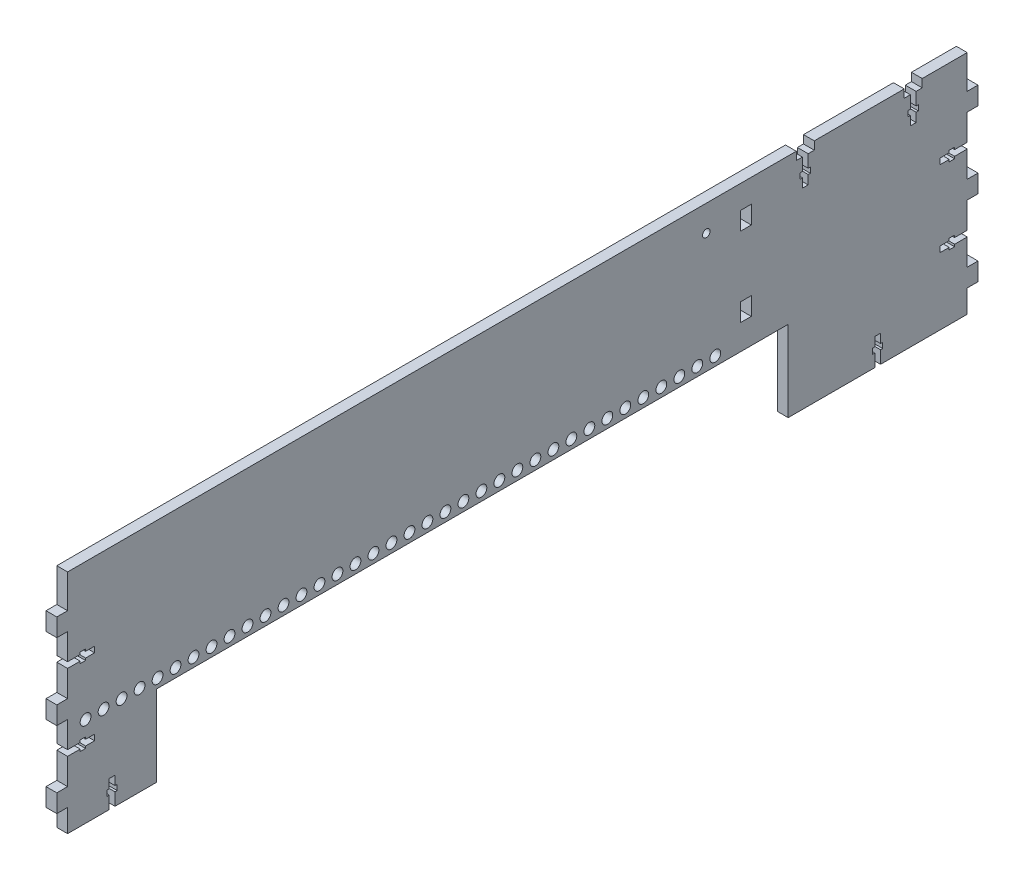
SolidWorks part; units mm, degrees
ref_plane "Front Plane" through (0, 0, 0) normal (0, 0, 1) x (1, 0, 0)
ref_plane "Top Plane" through (0, 0, 0) normal (0, 1, 0) x (1, 0, 0)
ref_plane "Right Plane" through (0, 0, 0) normal (1, 0, 0) x (0, 0, -1)
sketch "Sketch1" plane through (0, 0, 0) normal (1, 0, 0) x (0, 0, -1)
  line L1 (-250, -63) -> (250, -63)
  line L2 (-250, -63) -> (-250, 63)
  line L3 (-250, 63) -> (250, 63)
  line L4 (250, -63) -> (250, 63)
  line L5 (-250, -63) -> (250, 63) construction
  line L6 (-250, 63) -> (250, -63) construction
  point P0 (0, 0)
  dimension "D1" = 126
  dimension "D2" = 500
extrude "Boss-Extrude1" add sketch "Sketch1" along normal blind 6
sketch "Sketch4" plane through (0, 0, 250) normal (0, 0, 1) x (1, 0, 0)
  line L0 (0, 63) -> (0, -63) construction
  line L1 (0, 44.3321) -> (6, 44.3321)
  line L2 (0, 44.3321) -> (0, 34.3321)
  line L3 (0, 34.3321) -> (6, 34.3321)
  line L4 (6, 44.3321) -> (6, 34.3321)
  line L5 (6, 63) -> (6, -63) construction
  line L6 (0, 34.3321) -> (6, 34.3321) construction
  line L7 (0, -69) -> (0, 63) construction
  line L8 (6, 44.3321) -> (0, 44.3321) construction
  line L9 (0, -8) -> (6, -8) construction
  line L10 (0, -8) -> (6, -8)
  line L11 (0, -8) -> (0, 2)
  line L12 (0, 2) -> (6, 2)
  line L13 (6, -8) -> (6, 2)
  line L14 (6, -69) -> (6, 63) construction
  line L15 (6, 2) -> (0, 2) construction
  line L16 (6, -40.3321) -> (0, -40.3321) construction
  line L17 (0, -50.3321) -> (6, -50.3321)
  line L18 (0, -50.3321) -> (0, -40.3321)
  line L19 (0, -40.3321) -> (6, -40.3321)
  line L20 (6, -50.3321) -> (6, -40.3321)
  line L21 (0, -50.3321) -> (6, -50.3321) construction
extrude "Boss-Extrude2" add sketch "Sketch4" along normal blind 6
sketch "Sketch5" plane through (0, 0, 0) normal (-1, 0, 0) x (0, 0, 1)
  line L1 (250, 19.7661) -> (250, 16.5661) construction
  line L3 (250, 19.7661) -> (250, 16.5661) construction
  line L4 (250, -22.5661) -> (250, -25.7661) construction
  line L5 (250, -22.5661) -> (250, -25.7661) construction
  line L6 (250, 18.1661) -> (235, 18.1661) construction
  line L7 (250, -24.1661) -> (235, -24.1661) construction
  line L8 (250, -22.5661) -> (243, -22.5661)
  line L9 (250, 19.7661) -> (243, 19.7661)
  line L10 (250, -25.7661) -> (243, -25.7661)
  line L11 (250, 16.5661) -> (243, 16.5661)
  line L12 (250, -22.5661) -> (250, -25.7661)
  line L13 (235, -22.5661) -> (235, -25.7661)
  line L14 (250, 19.7661) -> (250, 16.5661)
  line L15 (235, 19.7661) -> (235, 16.5661)
  line L16 (240, 16.5661) -> (235, 16.5661)
  line L17 (243, 15.3661) -> (240, 15.3661)
  line L18 (243, 15.3661) -> (243, 16.5661)
  line L19 (243, 20.9661) -> (240, 20.9661)
  line L20 (240, 15.3661) -> (240, 16.5661)
  line L21 (243, 15.3661) -> (240, 20.9661) construction
  line L22 (243, 20.9661) -> (240, 15.3661) construction
  line L23 (243, -26.9661) -> (240, -26.9661)
  line L24 (243, -26.9661) -> (243, -25.7661)
  line L25 (243, -21.3661) -> (240, -21.3661)
  line L26 (240, -26.9661) -> (240, -25.7661)
  line L27 (243, -26.9661) -> (240, -21.3661) construction
  line L28 (243, -21.3661) -> (240, -26.9661) construction
  line L29 (250, 16.5661) -> (235, 16.5661) construction
  line L30 (243, 19.7661) -> (243, 20.9661)
  line L31 (240, 19.7661) -> (235, 19.7661)
  line L32 (250, 19.7661) -> (235, 19.7661) construction
  line L33 (240, 19.7661) -> (240, 20.9661)
  line L34 (240, -22.5661) -> (235, -22.5661)
  line L35 (250, -22.5661) -> (235, -22.5661) construction
  line L36 (240, -22.5661) -> (240, -21.3661)
  line L37 (240, -25.7661) -> (235, -25.7661)
  line L38 (250, -25.7661) -> (235, -25.7661) construction
  line L39 (243, -22.5661) -> (243, -21.3661)
  point P20 (241.5, 18.1661)
  point P25 (241.5, -24.1661)
  line M35 (250, -40.3321) -> (250, -8)
  line M39 (250, 2) -> (250, 34.3321)
  dimension "D3" = 1.6
  dimension "D4" = 7
  dimension "D5" = 3
  dimension "D6" = 5.6
  dimension "D1" = 15
  dimension "D7" = 7
  dimension "D8" = 3
  dimension "D9" = 5.6
  dimension "D2" = 1.6
extrude "Cut-Extrude3" cut sketch "Sketch5" against normal up to next contours L12 | L8 L39 L25 L36 L34 L13 L37 L26 L23 L24 L10 M35 | L33 L31 L15 L16 L20 L17 L18 L11 L9 L30 L19 M39 region at (0, -24.1661, 242.3696) region at (0, 18.1661, 242.3696)
sketch "Sketch6" plane through (0, 0, -250) normal (0, 0, -1) x (-1, 0, 0)
  line L0 (0, 44.3321) -> (0, 34.3321) construction
  line L1 (0, 34.3321) -> (-6, 34.3321) construction
  line L2 (-6, 34.3321) -> (-6, 44.3321) construction
  line L3 (-6, 44.3321) -> (0, 44.3321) construction
  line L4 (0, 2) -> (0, -8) construction
  line L5 (0, -8) -> (-6, -8) construction
  line L6 (-6, -8) -> (-6, 2) construction
  line L7 (-6, 2) -> (0, 2) construction
  line L8 (0, -40.3321) -> (0, -50.3321) construction
  line L9 (0, -50.3321) -> (-6, -50.3321) construction
  line L10 (-6, -50.3321) -> (-6, -40.3321) construction
  line L11 (-6, -40.3321) -> (0, -40.3321) construction
  line L12 (0, 44.3321) -> (0, 34.3321)
  line L13 (0, 34.3321) -> (-6, 34.3321)
  line L14 (-6, 34.3321) -> (-6, 44.3321)
  line L15 (-6, 44.3321) -> (0, 44.3321)
  line L16 (0, 2) -> (0, -8)
  line L17 (0, -8) -> (-6, -8)
  line L18 (-6, -8) -> (-6, 2)
  line L19 (-6, 2) -> (0, 2)
  line L20 (0, -40.3321) -> (0, -50.3321)
  line L21 (0, -50.3321) -> (-6, -50.3321)
  line L22 (-6, -50.3321) -> (-6, -40.3321)
  line L23 (-6, -40.3321) -> (0, -40.3321)
extrude "Boss-Extrude3" add sketch "Sketch6" along normal blind 6
sketch "Sketch7" plane through (0, 0, 0) normal (-1, 0, 0) x (0, 0, 1)
  line L0 (243, 16.5661) -> (250, 16.5661) construction
  line L2 (243, 16.5661) -> (243, 15.3661) construction
  line L3 (240, 15.3661) -> (243, 15.3661) construction
  line L4 (240, 16.5661) -> (240, 15.3661) construction
  line L5 (235, 16.5661) -> (240, 16.5661) construction
  line L6 (235, 16.5661) -> (235, 19.7661) construction
  line L7 (235, 19.7661) -> (240, 19.7661) construction
  line L8 (240, 20.9661) -> (240, 19.7661) construction
  line L9 (240, 20.9661) -> (243, 20.9661) construction
  line L10 (243, 20.9661) -> (243, 19.7661) construction
  line L11 (243, 19.7661) -> (250, 19.7661) construction
  line L12 (243, 16.5661) -> (250, 16.5661) construction
  line L13 (243, 16.5661) -> (243, 15.3661) construction
  line L14 (240, 15.3661) -> (243, 15.3661) construction
  line L15 (240, 16.5661) -> (240, 15.3661) construction
  line L16 (235, 16.5661) -> (240, 16.5661) construction
  line L17 (235, 16.5661) -> (235, 19.7661) construction
  line L18 (235, 19.7661) -> (240, 19.7661) construction
  line L19 (240, 20.9661) -> (240, 19.7661) construction
  line L20 (240, 20.9661) -> (243, 20.9661) construction
  line L21 (243, 20.9661) -> (243, 19.7661) construction
  line L22 (243, 19.7661) -> (250, 19.7661) construction
  line L23 (235, -25.7661) -> (240, -25.7661) construction
  line L24 (240, -25.7661) -> (240, -26.9661) construction
  line L25 (240, -26.9661) -> (243, -26.9661) construction
  line L26 (243, -25.7661) -> (243, -26.9661) construction
  line L27 (243, -25.7661) -> (250, -25.7661) construction
  line L28 (243, -22.5661) -> (250, -22.5661) construction
  line L29 (243, -21.3661) -> (243, -22.5661) construction
  line L30 (240, -21.3661) -> (243, -21.3661) construction
  line L31 (240, -21.3661) -> (240, -22.5661) construction
  line L32 (235, -22.5661) -> (240, -22.5661) construction
  line L33 (235, -25.7661) -> (235, -22.5661) construction
  line L34 (235, -25.7661) -> (240, -25.7661) construction
  line L35 (240, -25.7661) -> (240, -26.9661) construction
  line L36 (240, -26.9661) -> (243, -26.9661) construction
  line L37 (243, -25.7661) -> (243, -26.9661) construction
  line L38 (243, -25.7661) -> (250, -25.7661) construction
  line L39 (243, -22.5661) -> (250, -22.5661) construction
  line L40 (243, -21.3661) -> (243, -22.5661) construction
  line L41 (240, -21.3661) -> (243, -21.3661) construction
  line L42 (240, -21.3661) -> (240, -22.5661) construction
  line L43 (235, -22.5661) -> (240, -22.5661) construction
  line L44 (235, -25.7661) -> (235, -22.5661) construction
  line L45 (0, 0) -> (0, 57.5645) construction
  line L46 (-235, -25.7661) -> (-235, -22.5661)
  line L47 (-235, -22.5661) -> (-240, -22.5661)
  line L48 (-240, -21.3661) -> (-240, -22.5661)
  line L49 (-240, -21.3661) -> (-243, -21.3661)
  line L50 (-243, -21.3661) -> (-243, -22.5661)
  line L51 (-243, -22.5661) -> (-250, -22.5661)
  line L52 (-243, -25.7661) -> (-250, -25.7661)
  line L53 (-243, -25.7661) -> (-243, -26.9661)
  line L54 (-240, -26.9661) -> (-243, -26.9661)
  line L55 (-240, -25.7661) -> (-240, -26.9661)
  line L56 (-235, -25.7661) -> (-240, -25.7661)
  line L57 (-243, 19.7661) -> (-250, 19.7661)
  line L58 (-243, 20.9661) -> (-243, 19.7661)
  line L59 (-240, 20.9661) -> (-243, 20.9661)
  line L60 (-240, 20.9661) -> (-240, 19.7661)
  line L61 (-235, 19.7661) -> (-240, 19.7661)
  line L62 (-235, 16.5661) -> (-235, 19.7661)
  line L63 (-235, 16.5661) -> (-240, 16.5661)
  line L64 (-240, 16.5661) -> (-240, 15.3661)
  line L65 (-240, 15.3661) -> (-243, 15.3661)
  line L66 (-243, 16.5661) -> (-243, 15.3661)
  line L67 (-243, 16.5661) -> (-250, 16.5661)
  line L68 (-250, 19.7661) -> (-250, 16.5661)
  line L69 (-250, -22.5661) -> (-250, -25.7661)
extrude "Cut-Extrude4" cut sketch "Sketch7" against normal up to next
sketch "Sketch8" plane through (0, 0, 0) normal (-1, 0, 0) x (0, 0, 1)
  line L0 (200, -18.55) -> (-150, -18.55) construction
  line L1 (200, -18.55) -> (-150, -18.55) construction
  line L2 (200, -18.55) -> (200, -63) construction
  line L3 (200, -18.55) -> (200, -63) construction
  line L186 (-150, -18.55) -> (-150, -63) construction
  line L187 (-150, -63) -> (200, -63) construction
  line L188 (200.5, -18.05) -> (200.5, -63)
  line L189 (200.5, -18.05) -> (-150.5, -18.05)
  line L190 (-150.5, -18.05) -> (-150.5, -63)
  line L191 (-150.5, -63) -> (200.5, -63)
  dimension "D1" = 0.5
extrude "Cut-Extrude5" cut sketch "Sketch8" against normal up to next
sketch "Sketch11" plane through (6, 0, 0) normal (1, 0, 0) x (0, 0, -1)
  line L0 (130, 40) -> (130, 50) construction
  line L1 (130, 50) -> (124, 50) construction
  line L2 (124, 50) -> (124, 40) construction
  line L3 (124, 40) -> (130, 40) construction
  line L4 (130, -4) -> (130, 6) construction
  line L5 (130, 6) -> (124, 6) construction
  line L6 (124, 6) -> (124, -4) construction
  line L7 (124, -4) -> (130, -4) construction
  line L8 (130, 40) -> (130, 50)
  line L9 (130, 50) -> (124, 50)
  line L10 (124, 50) -> (124, 40)
  line L11 (124, 40) -> (130, 40)
  line L12 (130, -4) -> (130, 6)
  line L13 (130, 6) -> (124, 6)
  line L14 (124, 6) -> (124, -4)
  line L15 (124, -4) -> (130, -4)
extrude "Cut-Extrude8" cut sketch "Sketch11" against normal up to next
sketch "Sketch12" plane through (0, 0, 0) normal (-1, 0, 0) x (0, 0, 1)
  line L0 (-124, 50) -> (-124, 40) construction
  line L1 (-250, 63) -> (250, 63) construction
  circle A0 centre (-105, 48.5) radius 2.1
  dimension "D1" = 19
  dimension "D3" = 4.2
  dimension "D2" = 14.5
extrude "Cut-Extrude9" cut sketch "Sketch12" against normal up to next
sketch "Sketch13" plane through (0, 63, 0) normal (0, 1, 0) x (1, 0, 0)
  line L0 (6, 250) -> (6, -250) construction
  line L1 (0, 215) -> (6, 215)
  line L2 (0, 215) -> (0, 225)
  line L3 (0, 225) -> (6, 225)
  line L4 (6, 215) -> (6, 225)
  line L5 (0, 215) -> (6, 225) construction
  line L6 (0, 225) -> (6, 215) construction
  line L7 (6, 225) -> (0, 225) construction
  line L8 (6, 165) -> (0, 165) construction
  line L9 (0, 155) -> (6, 155)
  line L10 (0, 155) -> (0, 165)
  line L11 (0, 165) -> (6, 165)
  line L12 (6, 155) -> (6, 165)
  line L13 (0, 155) -> (6, 165) construction
  line L14 (0, 165) -> (6, 155) construction
  point P0 (3, 220)
  point P10 (3, 160)
extrude "Cut-Extrude10" cut sketch "Sketch13" against normal blind 4.5
sketch "Sketch14" plane through (0, 0, 0) normal (-1, 0, 0) x (0, 0, 1)
  circle A0 centre (240, -13) radius 3 construction
  circle A1 centre (240, -13) radius 3
  circle A2 centre (230, -13) radius 3
  circle A3 centre (220, -13) radius 3
  circle A4 centre (210, -13) radius 3
  circle A5 centre (200, -13) radius 3
  circle A6 centre (190, -13) radius 3
  circle A7 centre (180, -13) radius 3
  circle A8 centre (170, -13) radius 3
  circle A9 centre (160, -13) radius 3
  circle A10 centre (150, -13) radius 3
  circle A11 centre (140, -13) radius 3
  circle A12 centre (130, -13) radius 3
  circle A13 centre (120, -13) radius 3
  circle A14 centre (110, -13) radius 3
  circle A15 centre (100, -13) radius 3
  circle A16 centre (90, -13) radius 3
  circle A17 centre (80, -13) radius 3
  circle A18 centre (70, -13) radius 3
  circle A19 centre (60, -13) radius 3
  circle A20 centre (50, -13) radius 3
  circle A21 centre (40, -13) radius 3
  circle A22 centre (30, -13) radius 3
  circle A23 centre (20, -13) radius 3
  circle A24 centre (10, -13) radius 3
  circle A25 centre (0, -13) radius 3
  circle A26 centre (-10, -13) radius 3
  circle A27 centre (-20, -13) radius 3
  circle A28 centre (-30, -13) radius 3
  circle A29 centre (-40, -13) radius 3
  circle A30 centre (-50, -13) radius 3
  circle A31 centre (-60, -13) radius 3
  circle A32 centre (-70, -13) radius 3
  circle A33 centre (-80, -13) radius 3
  circle A34 centre (-90, -13) radius 3
  circle A35 centre (-100, -13) radius 3
  circle A36 centre (-110, -13) radius 3
  dimension "D1" = 36
extrude "Cut-Extrude11" cut sketch "Sketch14" against normal up to next (6 mm away)
sketch "Sketch15" plane through (6, 0, 0) normal (1, 0, 0) x (0, 0, -1)
  line L0 (160, 58.5) -> (160, 43.5) construction
  line L1 (155, 58.5) -> (165, 58.5) construction
  line L2 (220, 58.5) -> (220, 43.5) construction
  line L3 (215, 58.5) -> (225, 58.5) construction
  line L4 (160, 43.5) -> (220, 43.5) construction
  line L5 (190, 43.5) -> (190, 63) construction
  line L6 (215, 63) -> (165, 63) construction
  line L7 (158.4, 58.5) -> (158.4, 51.5)
  line L8 (161.6, 58.5) -> (161.6, 51.5)
  line L9 (158.4, 58.5) -> (161.6, 58.5)
  line L10 (158.4, 43.5) -> (161.6, 43.5)
  line L11 (161.6, 48.5) -> (162.8, 48.5)
  line L12 (157.2, 51.5) -> (158.4, 51.5)
  line L13 (157.2, 51.5) -> (157.2, 48.5)
  line L14 (157.2, 48.5) -> (158.4, 48.5)
  line L15 (162.8, 51.5) -> (162.8, 48.5)
  line L16 (157.2, 51.5) -> (162.8, 48.5) construction
  line L17 (157.2, 48.5) -> (162.8, 51.5) construction
  line L18 (161.6, 51.5) -> (162.8, 51.5)
  line L19 (158.4, 48.5) -> (158.4, 43.5)
  line L20 (158.4, 58.5) -> (158.4, 43.5) construction
  line L21 (161.6, 48.5) -> (161.6, 43.5)
  line L22 (161.6, 58.5) -> (161.6, 43.5) construction
  line L23 (222.8, 48.5) -> (217.2, 51.5) construction
  line L24 (222.8, 51.5) -> (217.2, 48.5) construction
  line L25 (220, 58.5) -> (220, 43.5) construction
  line L26 (218.4, 48.5) -> (218.4, 43.5)
  line L27 (221.6, 48.5) -> (221.6, 43.5)
  line L28 (218.4, 51.5) -> (217.2, 51.5)
  line L29 (217.2, 51.5) -> (217.2, 48.5)
  line L30 (222.8, 48.5) -> (221.6, 48.5)
  line L31 (222.8, 51.5) -> (222.8, 48.5)
  line L32 (222.8, 51.5) -> (221.6, 51.5)
  line L33 (218.4, 48.5) -> (217.2, 48.5)
  line L34 (221.6, 43.5) -> (218.4, 43.5)
  line L35 (221.6, 58.5) -> (218.4, 58.5)
  line L36 (218.4, 58.5) -> (218.4, 51.5)
  line L37 (221.6, 58.5) -> (221.6, 51.5)
  point P16 (160, 50)
  point P37 (220, 50)
  dimension "D3" = 15
  dimension "D4" = 7
  dimension "D5" = 3
  dimension "D6" = 5.6
  dimension "D1" = 1.6
  dimension "D2" = 1.6
extrude "Cut-Extrude12" cut sketch "Sketch15" against normal up to next
sketch "Sketch16" plane through (6, 0, 0) normal (1, 0, 0) x (0, 0, -1)
  line L0 (-250, -63) -> (-200.5, -63) construction
  line L1 (-250, -63) -> (-200.5, -63) construction
  line L2 (-225.25, -63) -> (-225.25, -48) construction
  line L3 (-223.65, -63) -> (-223.65, -56)
  line L4 (-226.85, -63) -> (-226.85, -56)
  line L5 (-223.65, -63) -> (-226.85, -63)
  line L6 (-223.65, -48) -> (-226.85, -48)
  line L7 (-223.65, -53) -> (-223.65, -48)
  line L8 (-228.05, -56) -> (-226.85, -56)
  line L9 (-228.05, -56) -> (-228.05, -53)
  line L10 (-228.05, -53) -> (-226.85, -53)
  line L11 (-222.45, -56) -> (-222.45, -53)
  line L12 (-228.05, -56) -> (-222.45, -53) construction
  line L13 (-228.05, -53) -> (-222.45, -56) construction
  line L14 (-223.65, -63) -> (-223.65, -48) construction
  line L15 (-223.65, -53) -> (-222.45, -53)
  line L16 (-226.85, -53) -> (-226.85, -48)
  line L17 (-226.85, -63) -> (-226.85, -48) construction
  line L18 (-223.65, -56) -> (-222.45, -56)
  line L19 (150.5, -63) -> (250, -63) construction
  line L20 (150.5, -63) -> (250, -63) construction
  line L21 (200.25, -63) -> (200.25, -48) construction
  line L22 (201.85, -63) -> (201.85, -56)
  line L23 (198.65, -63) -> (198.65, -56)
  line L24 (201.85, -63) -> (198.65, -63)
  line L25 (201.85, -48) -> (198.65, -48)
  line L26 (201.85, -56) -> (203.05, -56)
  line L27 (197.45, -56) -> (198.65, -56)
  line L28 (197.45, -56) -> (197.45, -53)
  line L29 (197.45, -53) -> (198.65, -53)
  line L30 (203.05, -56) -> (203.05, -53)
  line L31 (197.45, -56) -> (203.05, -53) construction
  line L32 (197.45, -53) -> (203.05, -56) construction
  line L33 (201.85, -53) -> (201.85, -48)
  line L34 (201.85, -63) -> (201.85, -48) construction
  line L35 (201.85, -53) -> (203.05, -53)
  line L36 (198.65, -53) -> (198.65, -48)
  line L37 (198.65, -63) -> (198.65, -48) construction
  point P8 (-225.25, -54.5)
  point P25 (200.25, -54.5)
  dimension "D1" = 15
  dimension "D4" = 7
  dimension "D5" = 3
  dimension "D6" = 5.6
  dimension "D2" = 1.6
  dimension "D3" = 1.6
  dimension "D7" = 1.6
  dimension "D8" = 1.6
extrude "Cut-Extrude13" cut sketch "Sketch16" against normal through all
